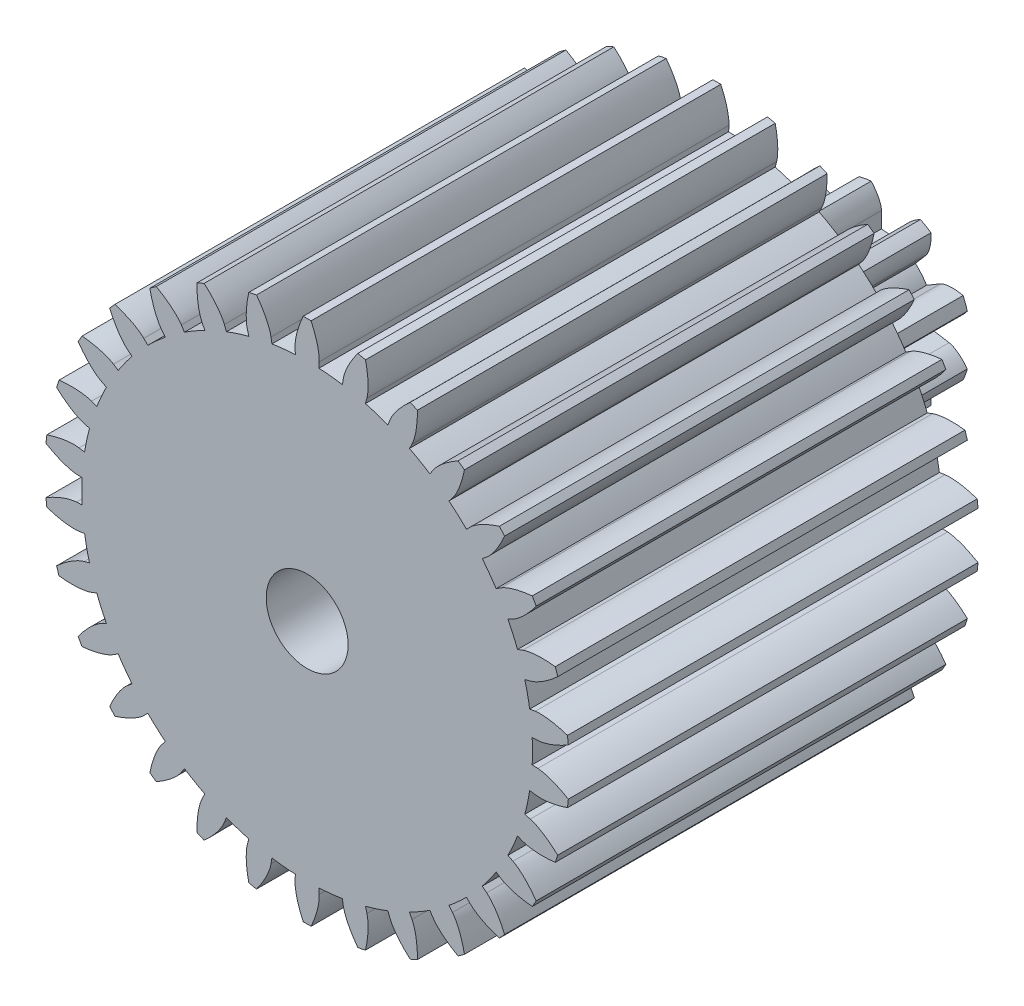
SolidWorks part; units mm, degrees
ref_plane "前视基准面" through (0, 0, 0) normal (0, 0, 1) x (1, 0, 0)
ref_plane "上视基准面" through (0, 0, 0) normal (0, 1, 0) x (1, 0, 0)
ref_plane "右视基准面" through (0, 0, 0) normal (1, 0, 0) x (0, 0, -1)
other "Configuration Table"
sketch "草图1" plane through (0, 0, 0) normal (0, 0, 1) x (1, 0, 0)
  line L0 (0, 0) -> (1.8, 0) construction
  line L1 (0, 0) -> (1.7727, 0.3126) construction
  line L2 (0, 0) -> (1.6688, 0.276)
  line L3 (1.7727, 0.3126) -> (1.7727, -0.3126) construction
  line L4 (0, 0) -> (1.6688, -0.276)
  circle A0 centre (0, 0) radius 2.2
  circle A1 centre (0, 0) radius 1.8 construction
  circle A2 centre (0, 0) radius 1.3
  circle A3 centre (0, 0) radius 1.6914 construction
  circle A4 centre (0, 0) radius 1
  spline S0 degree 4 poles (1.6688, 0.276) (1.6815, 0.2781) (1.7165, 0.2867) (1.7804, 0.3134) (1.8769, 0.3705) (1.9892, 0.4631) (2.115, 0.6012) (2.2366, 0.7836) (2.3401, 1.0009) (2.4181, 1.2482) (2.465, 1.503) (2.4828, 1.7615) (2.473, 2.0332) (2.4258, 2.3665) (2.3192, 2.7541) (2.1304, 3.1816) (1.8506, 3.6185) (1.5097, 4.0103) (1.1213, 4.3527) (0.6893, 4.6421) (0.2307, 4.8777) (-0.2607, 5.0574) (-0.7542, 5.1833) (-1.2841, 5.2523) (-1.6863, 5.2693) (-2.1385, 5.2469) (-2.3948, 5.2166) (-2.6865, 5.1734) (-2.8298, 5.138) (-2.9571, 5.1118) (-2.9949, 5.1006) (-3.0222, 5.094) (-3.037, 5.0905) knots 0 0 0 0 0 0.005604 0.015718 0.02996 0.048734 0.068727 0.096889 0.125051 0.153212 0.181374 0.209535 0.237696 0.271429 0.327752 0.384075 0.440398 0.496721 0.553044 0.609367 0.66569 0.722013 0.778336 0.834659 0.890982 0.909091 0.954545 0.977273 0.988636 0.994318 1 1 1 1 1 construction
  spline S1 degree 4 poles (1.6688, 0.276) (1.6815, 0.2781) (1.7165, 0.2867) (1.7804, 0.3134) (1.8769, 0.3705) (1.9892, 0.4631) (2.115, 0.6012) (2.2366, 0.7836) (2.3401, 1.0009) (2.4181, 1.2482) (2.465, 1.503) (2.4828, 1.7615) (2.473, 2.0332) (2.4258, 2.3665) (2.3192, 2.7541) (2.1304, 3.1816) (1.8506, 3.6185) (1.5097, 4.0103) (1.1213, 4.3527) (0.6893, 4.6421) (0.2307, 4.8777) (-0.2607, 5.0574) (-0.7542, 5.1833) (-1.2841, 5.2523) (-1.6863, 5.2693) (-2.0219, 5.2526) (-2.1774, 5.2392) (-2.215, 5.2356) knots 0 0 0 0 0 0.005604 0.015718 0.02996 0.048734 0.068727 0.096889 0.125051 0.153212 0.181374 0.209535 0.237696 0.271429 0.327752 0.384075 0.440398 0.496721 0.553044 0.609367 0.66569 0.722013 0.778336 0.834659 0.890982 0.909091 0.909091 0.909091 0.909091 0.909091
  spline S2 degree 4 poles (1.6688, -0.276) (1.6815, -0.2781) (1.7165, -0.2867) (1.7804, -0.3134) (1.8769, -0.3705) (1.9892, -0.4631) (2.115, -0.6012) (2.2366, -0.7836) (2.3401, -1.0009) (2.4181, -1.2482) (2.465, -1.503) (2.4828, -1.7615) (2.473, -2.0332) (2.4258, -2.3665) (2.3192, -2.7541) (2.1304, -3.1816) (1.8506, -3.6185) (1.5097, -4.0103) (1.1213, -4.3527) (0.6893, -4.6421) (0.2307, -4.8777) (-0.2607, -5.0574) (-0.7542, -5.1833) (-1.2841, -5.2523) (-1.6863, -5.2693) (-2.1385, -5.2469) (-2.3948, -5.2166) (-2.6865, -5.1734) (-2.8298, -5.138) (-2.9571, -5.1118) (-2.9949, -5.1006) (-3.0222, -5.094) (-3.037, -5.0905) knots 0 0 0 0 0 0.005604 0.015718 0.02996 0.048734 0.068727 0.096889 0.125051 0.153212 0.181374 0.209535 0.237696 0.271429 0.327752 0.384075 0.440398 0.496721 0.553044 0.609367 0.66569 0.722013 0.778336 0.834659 0.890982 0.909091 0.954545 0.977273 0.988636 0.994318 1 1 1 1 1 construction
  spline S3 degree 4 poles (1.6688, -0.276) (1.6815, -0.2781) (1.7165, -0.2867) (1.7804, -0.3134) (1.8769, -0.3705) (1.9892, -0.4631) (2.115, -0.6012) (2.2366, -0.7836) (2.3401, -1.0009) (2.4181, -1.2482) (2.465, -1.503) (2.4828, -1.7615) (2.473, -2.0332) (2.4258, -2.3665) (2.3192, -2.7541) (2.1304, -3.1816) (1.8506, -3.6185) (1.5097, -4.0103) (1.1213, -4.3527) (0.6893, -4.6421) (0.2307, -4.8777) (-0.2607, -5.0574) (-0.7542, -5.1833) (-1.2841, -5.2523) (-1.6863, -5.2693) (-2.0219, -5.2526) (-2.1774, -5.2392) (-2.215, -5.2356) knots 0 0 0 0 0 0.005604 0.015718 0.02996 0.048734 0.068727 0.096889 0.125051 0.153212 0.181374 0.209535 0.237696 0.271429 0.327752 0.384075 0.440398 0.496721 0.553044 0.609367 0.66569 0.722013 0.778336 0.834659 0.890982 0.909091 0.909091 0.909091 0.909091 0.909091
  point P15 (1.7727, 0)
  dimension "齿顶圆直径" = 4.4
  dimension "分度圆直径" = 3.6
  dimension "齿根圆直径" = 2.6
  dimension "基圆直径" = 3.3829
  dimension "内孔直径" = 2
  dimension "渐近线镜像线夹角" = 10
extrude "凸台-拉伸1" add sketch "草图1" along normal blind 4 contours A0 | A4
extrude "切除-拉伸1" cut sketch "草图1<3>" along normal through all contours A2 S3 A0 S1 region at (1.8185, 0, 0)
sketch "草图1<3>" plane through (0, 0, 0) normal (0, 0, 1) x (1, 0, 0) same geometry as "草图1"
pattern_circular "阵列(圆周)1" count 9 every 40 about axis through (0, 0, 4) along (0, 0, 1) of "切除-拉伸1"
sketch "草图2" plane through (0, 0, 4) normal (0, 0, 1) x (1, 0, 0)
  line L0 (0, 0) -> (6, 0) construction
  line L1 (0, 0) -> (5.6304, 0.2951)
  line L2 (0, 0) -> (5.6304, -0.2951)
  line L3 (5.6304, 0.2951) -> (5.6304, -0.2951) construction
  circle A0 centre (0, 0) radius 6 construction
  circle A1 centre (0, 0) radius 5.6382 construction
  circle A2 centre (0, 0) radius 5.5
  circle A3 centre (0, 0) radius 6.4
  circle A4 centre (0, 0) radius 1
  spline S0 degree 4 poles (5.6304, -0.2951) (5.6519, -0.2962) (5.6945, -0.3005) (5.8129, -0.3229) (6.032, -0.3922) (6.3509, -0.5432) (6.7529, -0.8142) (7.2143, -1.2331) (7.6755, -1.7994) (8.0876, -2.4877) (8.425, -3.2835) (8.6612, -4.1145) (8.8022, -4.9665) (8.8558, -5.871) (8.805, -6.9919) (8.5735, -8.3118) (8.0834, -9.7904) (7.2917, -11.3288) (6.2875, -12.7368) (5.1029, -13.9959) (3.7678, -15.0933) (2.3097, -16.0204) (0.9488, -16.6782) (-0.2638, -17.1311) (-1.2979, -17.4345) (-2.0325, -17.6082) (-2.6669, -17.7296) (-3.2005, -17.8126) (-3.6254, -17.868) (-4.0587, -17.9127) (-4.4801, -17.9466) (-4.8863, -17.9677) (-5.2165, -17.9791) (-5.5938, -17.9835) (-5.838, -17.9825) (-6.2326, -17.9752) (-6.5391, -17.9609) (-6.9112, -17.9398) (-7.2423, -17.9121) (-7.5988, -17.8777) (-7.9363, -17.8368) (-8.2008, -17.8012) (-8.3691, -17.7754) (-8.4565, -17.7619) knots 0 0 0 0 0 0.002802 0.005604 0.015718 0.02996 0.048734 0.068727 0.096889 0.125051 0.153212 0.181374 0.209535 0.237696 0.271429 0.327752 0.384075 0.440398 0.496721 0.553044 0.609367 0.66569 0.722013 0.750174 0.778336 0.806497 0.820578 0.834659 0.84874 0.86282 0.876901 0.890982 0.900036 0.909091 0.920455 0.931818 0.943182 0.954545 0.965909 0.977273 0.988636 1 1 1 1 1 construction
  spline S1 degree 4 poles (5.6304, -0.2951) (5.6519, -0.2962) (5.6945, -0.3005) (5.8129, -0.3229) (6.032, -0.3922) (6.3509, -0.5432) (6.7529, -0.8142) (7.2143, -1.2331) (7.6755, -1.7994) (8.0876, -2.4877) (8.425, -3.2835) (8.6612, -4.1145) (8.8022, -4.9665) (8.8558, -5.871) (8.805, -6.9919) (8.5735, -8.3118) (8.0834, -9.7904) (7.2917, -11.3288) (6.2875, -12.7368) (5.1029, -13.9959) (3.7678, -15.0933) (2.3097, -16.0204) (0.9488, -16.6782) (-0.2638, -17.1311) (-1.2979, -17.4345) (-2.0325, -17.6082) (-2.6669, -17.7296) (-3.2005, -17.8126) (-3.6254, -17.868) (-4.0587, -17.9127) (-4.4801, -17.9466) (-4.8863, -17.9677) (-5.2165, -17.9791) (-5.4954, -17.9824) (-5.6224, -17.9828) (-5.6854, -17.9827) knots 0 0 0 0 0 0.002802 0.005604 0.015718 0.02996 0.048734 0.068727 0.096889 0.125051 0.153212 0.181374 0.209535 0.237696 0.271429 0.327752 0.384075 0.440398 0.496721 0.553044 0.609367 0.66569 0.722013 0.750174 0.778336 0.806497 0.820578 0.834659 0.84874 0.86282 0.876901 0.890982 0.900036 0.909091 0.909091 0.909091 0.909091 0.909091
  spline S2 degree 4 poles (5.6304, 0.2951) (5.6519, 0.2962) (5.6945, 0.3005) (5.8129, 0.3229) (6.032, 0.3922) (6.3509, 0.5432) (6.7529, 0.8142) (7.2143, 1.2331) (7.6755, 1.7994) (8.0876, 2.4877) (8.425, 3.2835) (8.6612, 4.1145) (8.8022, 4.9665) (8.8558, 5.871) (8.805, 6.9919) (8.5735, 8.3118) (8.0834, 9.7904) (7.2917, 11.3288) (6.2875, 12.7368) (5.1029, 13.9959) (3.7678, 15.0933) (2.3097, 16.0204) (0.9488, 16.6782) (-0.2638, 17.1311) (-1.2979, 17.4345) (-2.0325, 17.6082) (-2.6669, 17.7296) (-3.2005, 17.8126) (-3.6254, 17.868) (-4.0587, 17.9127) (-4.4801, 17.9466) (-4.8863, 17.9677) (-5.2165, 17.9791) (-5.5938, 17.9835) (-5.838, 17.9825) (-6.2326, 17.9752) (-6.5391, 17.9609) (-6.9112, 17.9398) (-7.2423, 17.9121) (-7.5988, 17.8777) (-7.9363, 17.8368) (-8.2008, 17.8012) (-8.3691, 17.7754) (-8.4565, 17.7619) knots 0 0 0 0 0 0.002802 0.005604 0.015718 0.02996 0.048734 0.068727 0.096889 0.125051 0.153212 0.181374 0.209535 0.237696 0.271429 0.327752 0.384075 0.440398 0.496721 0.553044 0.609367 0.66569 0.722013 0.750174 0.778336 0.806497 0.820578 0.834659 0.84874 0.86282 0.876901 0.890982 0.900036 0.909091 0.920455 0.931818 0.943182 0.954545 0.965909 0.977273 0.988636 1 1 1 1 1 construction
  spline S3 degree 4 poles (5.6304, 0.2951) (5.6519, 0.2962) (5.6945, 0.3005) (5.8129, 0.3229) (6.032, 0.3922) (6.3509, 0.5432) (6.7529, 0.8142) (7.2143, 1.2331) (7.6755, 1.7994) (8.0876, 2.4877) (8.425, 3.2835) (8.6612, 4.1145) (8.8022, 4.9665) (8.8558, 5.871) (8.805, 6.9919) (8.5735, 8.3118) (8.0834, 9.7904) (7.2917, 11.3288) (6.2875, 12.7368) (5.1029, 13.9959) (3.7678, 15.0933) (2.3097, 16.0204) (0.9488, 16.6782) (-0.2638, 17.1311) (-1.2979, 17.4345) (-2.0325, 17.6082) (-2.6669, 17.7296) (-3.2005, 17.8126) (-3.6254, 17.868) (-4.0587, 17.9127) (-4.4801, 17.9466) (-4.8863, 17.9677) (-5.2165, 17.9791) (-5.4954, 17.9824) (-5.6224, 17.9828) (-5.6854, 17.9827) knots 0 0 0 0 0 0.002802 0.005604 0.015718 0.02996 0.048734 0.068727 0.096889 0.125051 0.153212 0.181374 0.209535 0.237696 0.271429 0.327752 0.384075 0.440398 0.496721 0.553044 0.609367 0.66569 0.722013 0.750174 0.778336 0.806497 0.820578 0.834659 0.84874 0.86282 0.876901 0.890982 0.900036 0.909091 0.909091 0.909091 0.909091 0.909091
  point P16 (5.6304, 0)
  dimension "内孔直径" = 2
  dimension "分度圆直径" = 12
  dimension "齿顶圆直径" = 12.8
  dimension "基圆直径" = 11.2763
  dimension "齿根圆直径" = 11
  dimension "渐开线镜像线夹角" = 3
extrude "凸台-拉伸2" add sketch "草图2" along normal blind 10 contours A3 | A4
extrude "切除-拉伸3" cut sketch "草图2<3>" along normal through all contours S3 L1 A2 L2 S1 A3 region at (6.002, 0, 4)
sketch "草图2<3>" plane through (0, 0, 4) normal (0, 0, 1) x (1, 0, 0) same geometry as "草图2"
pattern_circular "阵列(圆周)2" count 30 over 360 about axis through (0, 0, 14) along (0, 0, 1) of "切除-拉伸3"
equation "\"m\"= 0.4'模数"
equation "\"z\"= 9'齿数"
equation "\"a\"= 20度'压力角"
equation "\"d\"= \"m\" * \"z\"'分度圆直径"
equation "\"da\"= ( \"z\" + 2 ) * \"m\"'齿顶圆直径"
equation "\"df\"= ( \"z\" - 2.5 ) * \"m\"'齿根圆直径"
equation "\"s\"= 0.5 * PI * \"m\"'分度圆齿厚"
equation "\"r\"= 0.38 * \"m\"'齿根圆角"
equation "\"B\"= 0.3 * \"d\"'齿厚"
equation "\"db\"= \"m\" * \"z\" * cos ( \"a\" )'基圆直径"
equation "\"rb\"= \"db\" / 2'基圆半径"
equation "\"齿顶圆直径@草图1\"= \"da\""
equation "\"分度圆直径@草图1\"= \"d\""
equation "\"齿根圆直径@草图1\"= \"df\""
equation "\"基圆直径@草图1\"= \"db\""
equation "\"渐近线镜像线夹角@草图1\"= 360 / 4 / \"z\""
equation "\"h\"= 4mm'齿轮厚度"
equation "\"ir\"= 2mm'内孔直径"
equation "\"内孔直径@草图1\"= \"ir\""
equation "\"齿轮厚@凸台-拉伸1\"= \"h\""
equation "\"齿轮夹角@阵列(圆周)1\"= 360 / \"z\""
equation "\"齿数@阵列(圆周)1\"= \"z\""
equation "\"m1\"= 0.4'模数"
equation "\"z1\"= 30'齿数"
equation "\"a1\"= 20度'压力角"
equation "\"d1\"= \"m1\" * \"z1\"'分度圆直径"
equation "\"da1\"= ( \"z1\" + 2 ) * \"m1\"'齿顶圆直径"
equation "\"df1\"= ( \"z1\" - 2.5 ) * \"m1\"'齿根圆直径"
equation "\"s1\"= 0.5 * PI * \"m1\"'分度圆齿厚"
equation "\"r1\"= 0.38 * \"m1\"'齿根圆角"
equation "\"B1\"= 0.3 * \"d1\"'齿厚"
equation "\"db1\"= \"m1\" * \"z1\" * cos ( \"a1\" )'基圆直径"
equation "\"rb1\"= \"db1\" / 2'基圆半径"
equation "\"分度圆直径@草图2\"= \"d1\""
equation "\"齿顶圆直径@草图2\"= \"da1\""
equation "\"基圆直径@草图2\"= \"db1\""
equation "\"齿根圆直径@草图2\"= \"df1\""
equation "\"渐开线镜像线夹角@草图2\"= 360 / 4 / \"z1\""
equation "\"内孔直径@草图2\"= \"ir\""
equation "\"二层齿轮厚@凸台-拉伸2\" = \"h1\""
equation "\"h1\"= 10'齿轮厚度"
equation "\"二层齿数@阵列(圆周)2\"= \"z1\""
